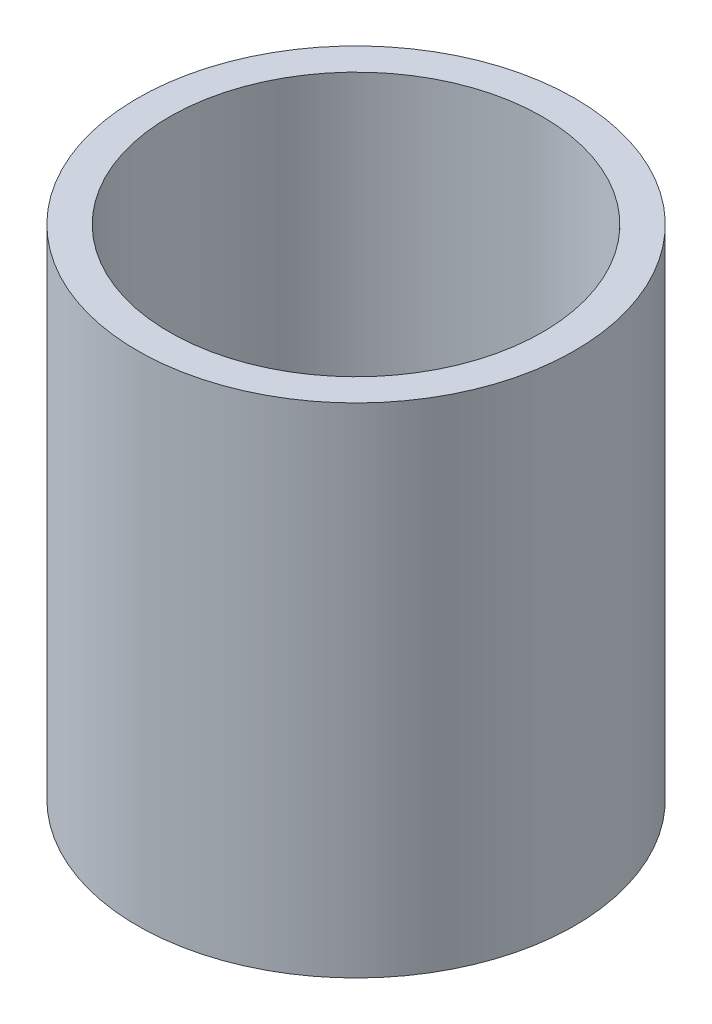
SolidWorks part; units mm, degrees
ref_plane "Front Plane" through (0, 0, 0) normal (0, 0, 1) x (1, 0, 0)
ref_plane "Top Plane" through (0, 0, 0) normal (0, 1, 0) x (1, 0, 0)
ref_plane "Right Plane" through (0, 0, 0) normal (1, 0, 0) x (0, 0, -1)
sketch "Sketch1" plane through (0, 0, 0) normal (0, 1, 0) x (1, 0, 0)
  circle A0 centre (0, 0) radius 37.9351
  circle A1 centre (0, 0) radius 32.3683
extrude "Boss-Extrude1" add sketch "Sketch1" along normal blind 86.4
